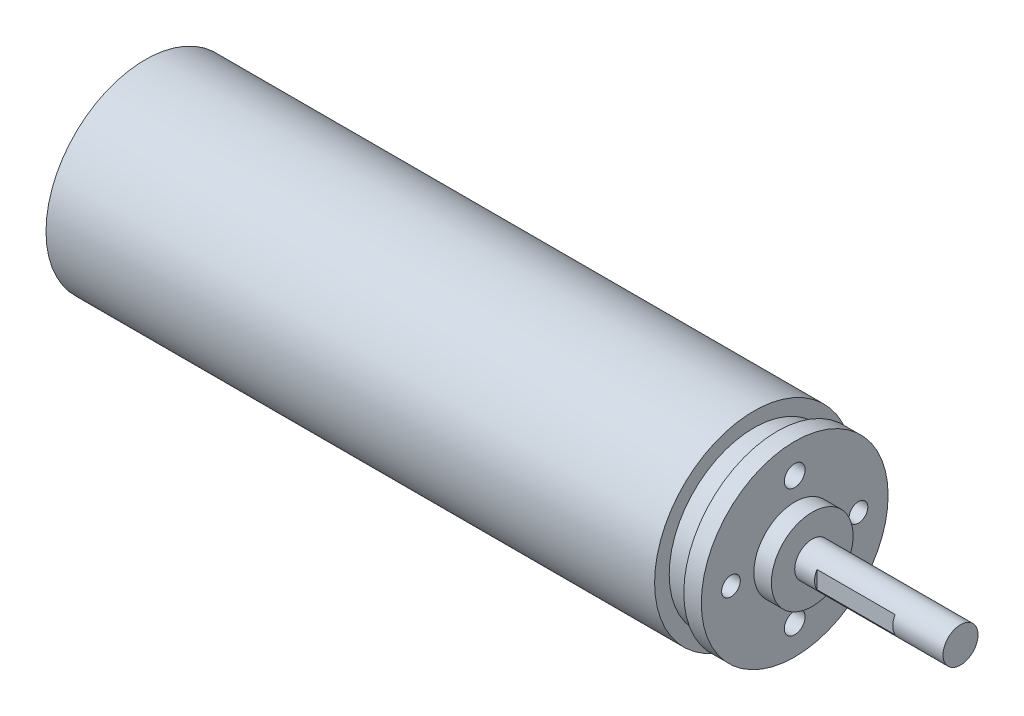
SolidWorks part; units mm, degrees
ref_plane "Front Plane" through (0, 0, 0) normal (0, 0, 1) x (1, 0, 0)
ref_plane "Top Plane" through (0, 0, 0) normal (0, 1, 0) x (1, 0, 0)
ref_plane "Right Plane" through (0, 0, 0) normal (1, 0, 0) x (0, 0, -1)
sketch "Sketch3" plane through (0, 0, 0) normal (0, 0, 1) x (1, 0, 0)
  line L0 (0, -8.5) -> (28.5, -8.5)
  line L1 (28.5, -8.5) -> (28.5, -7.25)
  line L2 (28.5, -7.25) -> (30.5, -7.25)
  line L3 (30.5, -7.25) -> (30.5, -8)
  line L4 (30.5, -8) -> (32, -8)
  line L5 (32, -3.5) -> (33.5, -3.5)
  line L6 (33.5, -3.5) -> (33.5, -1.5)
  line L7 (33.5, -1.5) -> (40.8882, -1.5)
  line L8 (40.8882, -1.5) -> (41.6616, -1.5)
  line L11 (32, -8) -> (32, -3.5)
  line L12 (41.6616, -1.5) -> (46.2, -1.5)
  line L13 (46.2, -1.5) -> (46.2, 0)
  line L14 (0, -8.5) -> (0, 0)
  line L15 (0, 0) -> (46.2, 0)
  dimension "D1" = 8.5
  dimension "D2" = 1.5
  dimension "D3" = 46.2
  dimension "D4" = 12.7
  dimension "D5" = 3.5
  dimension "D7" = 2
  dimension "D8" = 7.25
  dimension "D9" = 28.5
  dimension "D10" = 8
  dimension "D11" = 32
revolve "Revolve1" add sketch "Sketch3" angle 360 about L15
sketch "Sketch4" plane through (0, 0, 0) normal (0, 1, 0) x (1, 0, 0)
  line L0 (35.2, -1.5) -> (35.2, -1.3)
  line L1 (33.5, -1.5) -> (46.2, -1.5) construction
  line L2 (35.2, -1.3) -> (41.9, -1.3)
  line L3 (41.9, -1.3) -> (41.9, -1.5)
  line L4 (33.5, -1.5) -> (46.2, -1.5) construction
  line L5 (41.9, -1.5) -> (35.2, -1.5)
  line L6 (46.2, -1.5) -> (46.2, 1.5) construction
  dimension "D1" = 0.2
  dimension "D2" = 6.7
  dimension "D3" = 4.3
extrude "Cut-Extrude1" cut sketch "Sketch4" against normal blind 2.54 and the other way blind 2.54
hole_wizard "#2-56 Tapped Hole1" positions "Sketch6" profile "Sketch7" tap size "#2-56" standard "ANSI Inch"
sketch "Sketch6" plane through (32, 0, 0) normal (1, 0, 0) x (0, 0, -1)
  point P0 (0, 5.46)
  point P2 (0, -5.46)
  dimension "D1" = 5.46
  dimension "D2" = 5.46
  dimension "D3" = 0
  dimension "D4" = 0
sketch "Sketch7" plane through (32, 5.46, 0) normal (0, 1, 0) x (0, 0, -1)
  line L0 (0, 0) -> (0, 7.1382)
  line L1 (0, 7.1382) -> (0.889, 6.604)
  line L2 (0.889, 6.604) -> (0.889, 0)
  line L5 (0.889, 0) -> (0, 0)
  line L10 (0, 7.1382) -> (-0.889, 6.604) construction
  line L11 (0, -6.35) -> (0, 107.95) construction
  dimension "Tap Drill Dia." = 1.778
  dimension "Tap Drill Depth" = 6.604
  dimension "Drill Angle" = 118
cosmetic thread "Hole Thread1" parameters "D1"=4.318, "D2"=2.1844
cosmetic thread "Hole Thread2" parameters "D1"=4.318, "D2"=2.1844
hole_wizard "M2x0.4 Tapped Hole1" positions "Sketch9" profile "Sketch8" tap size "M2x0.4" standard "ANSI Metric"
sketch "Sketch9" plane through (32, 0, 0) normal (1, 0, 0) x (0, 0, -1)
  point P0 (-5.46, 0)
  point P2 (5.46, 0)
  dimension "D1" = 5.46
  dimension "D2" = 5.46
  dimension "D3" = 0
  dimension "D4" = 0
sketch "Sketch8" plane through (32, 0, 5.46) normal (0, 1, 0) x (0, 0, -1)
  line L0 (0, 0) -> (0, 6.5767)
  line L1 (0, 6.5767) -> (0.8, 6.096)
  line L2 (0.8, 6.096) -> (0.8, 0)
  line L5 (0.8, 0) -> (0, 0)
  line L10 (0, 6.5767) -> (-0.8, 6.096) construction
  line L11 (0, -6.35) -> (0, 107.95) construction
  dimension "Tap Drill Dia." = 1.6
  dimension "Tap Drill Depth" = 6.096
  dimension "Drill Angle" = 118
cosmetic thread "Hole Thread3" parameters "D1"=4.064, "D2"=2
cosmetic thread "Hole Thread4" parameters "D1"=4.064, "D2"=2
sketch "Sketch10" plane through (0, 0, 0) normal (-1, 0, 0) x (0, 0, 1)
  circle A0 centre (0, 0) radius 8.5
  dimension "D1" = 17
extrude "Boss-Extrude2" add sketch "Sketch10" along normal blind 23.622
